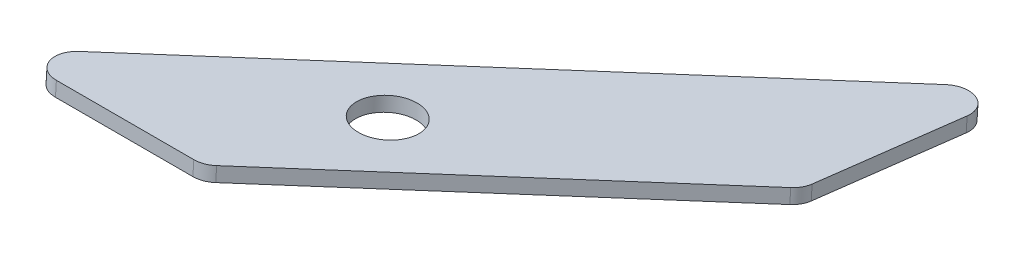
SolidWorks part; units mm, degrees
material "Plain Carbon Steel"
ref_plane "Front Plane" through (0, 0, 0) normal (0, 0, 1) x (1, 0, 0)
ref_plane "Top Plane" through (0, 0, 0) normal (0, 1, 0) x (1, 0, 0)
ref_plane "Right Plane" through (0, 0, 0) normal (1, 0, 0) x (0, 0, -1)
ref_axis "Axis1" through (200.0538, 113.7957, 921.4109) along (-0.061, 0.065, 0.996)
ref_plane "Plane1" through (0, 53.3914, -3.4869) normal (0, 0.9979, -0.0652) x (1, 0, 0)
ref_plane "Plane2" through (0, 40.7184, -2.6593) normal (0, -0.9979, 0.0652) x (-1, 0, 0)
sketch "Sketch1" plane through (0, 40.7184, -2.6593) normal (0, -0.9979, 0.0652) x (-1, 0, 0)
  line L0 (-171.1394, -1400.231) -> (-137.7936, -1433.5769)
  line L2 (181.7755, -1433.5769) -> (-181.7755, -1433.5769) construction
  line L3 (-137.7936, -1433.5769) -> (-115.3429, -1433.5769)
  line L4 (-115.3429, -1433.5769) -> (-172.5999, -1376.3198)
  line L5 (-172.5999, -1376.3198) -> (-171.1394, -1400.231)
  line L6 (-126.5682, -1433.5769) -> (-158.3182, -1401.8269) construction
  line L8 (-200.0538, -926.8682) -> (-169.1645, -1432.5629) construction
  line L9 (-181.61, -1433.5823) -> (181.61, -1433.5823) construction
  circle A0 centre (-142.4432, -1417.7019) radius 3.2639
  point P2 (-147.4836, -1417.7019)
  dimension "D1" = 6.5278
  dimension "D2" = 135
  dimension "D3" = 15.875
  dimension "D4" = 15.875
  dimension "D5" = 12.7
extrude "Boss-Extrude1" add sketch "Sketch1" along normal blind 1.5875
fillet "Fillet1" radius 2.54 4 edges at (172.5999, 129.6216, 1370.7864) (137.7936, 133.353, 1427.9217) (171.1394, 131.1799, 1394.6468) (115.3429, 133.353, 1427.9217)
